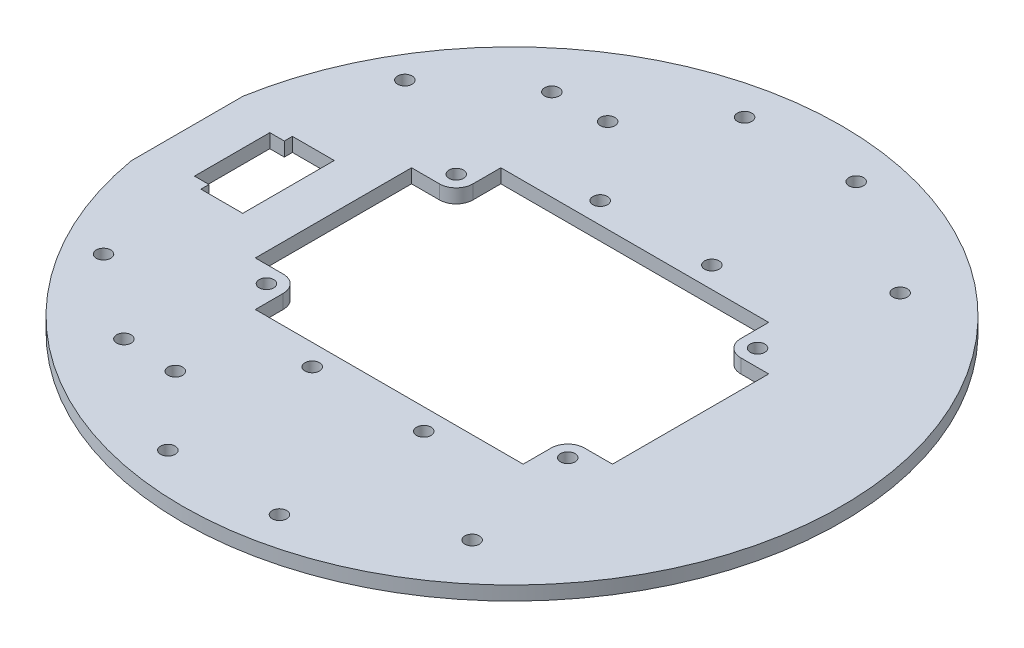
SolidWorks part; units mm, degrees
material "Acrylic (Medium-high impact)"
ref_plane "Front Plane" through (0, 0, 0) normal (0, 0, 1) x (1, 0, 0)
ref_plane "Top Plane" through (0, 0, 0) normal (0, 1, 0) x (1, 0, 0)
ref_plane "Right Plane" through (0, 0, 0) normal (1, 0, 0) x (0, 0, -1)
sketch "Sketch1" plane through (0, 0, 0) normal (0, 1, 0) x (1, 0, 0)
  line L0 (-73.9169, 12.7) -> (-73.9169, -12.7)
  line L1 (-73.9169, 12.7) -> (-73.9169, -12.7) construction
  line L2 (-34.29, 21.59) -> (34.29, 21.59) construction
  line L3 (34.29, 21.59) -> (34.29, -21.59) construction
  line L4 (34.29, -21.59) -> (-34.29, -21.59) construction
  line L5 (-34.29, -21.59) -> (-34.29, 21.59) construction
  line L6 (0, 21.59) -> (0, 75) construction
  line L7 (34.29, 0) -> (75, 0) construction
  line L8 (0, -25.4) -> (0, -21.59) construction
  line L9 (-34.29, 0) -> (-38.1, 0) construction
  line L10 (-30.48, 27.94) -> (30.48, 27.94)
  line L11 (-30.48, 27.94) -> (-30.48, 21.59)
  line L12 (0, 21.59) -> (0, 27.94) construction
  line L13 (30.48, 27.94) -> (30.48, 21.59)
  line L14 (34.29, 17.78) -> (40.64, 17.78)
  line L16 (34.29, -17.78) -> (40.64, -17.78)
  line L17 (40.64, 17.78) -> (40.64, -17.78)
  line L19 (30.48, -21.59) -> (30.48, -27.94)
  line L20 (30.48, -27.94) -> (-30.48, -27.94)
  line L21 (-30.48, -21.59) -> (-30.48, -27.94)
  line L22 (-40.64, -17.78) -> (-34.29, -17.78)
  line L23 (-40.64, -17.78) -> (-40.64, 17.78)
  line L24 (-40.64, 17.78) -> (-34.29, 17.78)
  line L28 (-24.25, -35.9484) -> (24.25, -35.9484) construction
  line L29 (24.25, -35.9484) -> (24.25, -62.4484) construction
  line L30 (-12.7, -35.9484) -> (-12.7, -32.7734) construction
  line L31 (24.25, -62.4484) -> (-24.25, -62.4484) construction
  line L32 (-24.25, -62.4484) -> (-24.25, -35.9484) construction
  line L33 (-24.25, -62.4484) -> (-27.1489, -69.9138) construction
  line L34 (24.25, -62.4484) -> (27.1489, -69.9138) construction
  line L35 (-24.25, -35.9484) -> (-24.25, -27.94) construction
  line L36 (0, -35.9484) -> (0, -62.4484) construction
  line L37 (-50.865, 0) -> (-40.64, 0) construction
  line L38 (-27.425, -49.1984) -> (-24.25, -49.1984) construction
  line L39 (-12.7, -65.6234) -> (-12.7, -62.4484) construction
  line L40 (-63.692, 8.5725) -> (-60.39, 8.5725)
  line L41 (-63.692, 8.5725) -> (-63.692, -8.5725)
  line L42 (-63.692, -8.5725) -> (-60.39, -8.5725)
  line L43 (-50.865, 8.5725) -> (-50.865, -8.5725)
  line L44 (-60.39, 8.5725) -> (-60.39, 10.414)
  line L45 (-60.39, 10.414) -> (-50.865, 10.414)
  line L46 (-50.865, 10.414) -> (-50.865, 8.5725)
  line L47 (-60.39, -8.5725) -> (-60.39, -10.414)
  line L48 (-60.39, -10.414) -> (-50.865, -10.414)
  line L49 (-50.865, -10.414) -> (-50.865, -8.5725)
  line L50 (-63.692, 0) -> (-73.9169, 0) construction
  line L51 (55.1757, 50.8) -> (55.1757, -50.8) construction
  arc A0 (-73.9169, -12.7) -> (-73.9169, 12.7) centre (0, 0) ccw
  arc A1 (55.356, -50.6035) -> (55.356, 50.6035) centre (0, 0) ccw construction
  circle A2 centre (-34.29, 21.59) radius 1.651
  circle A3 centre (34.29, 21.59) radius 1.651
  circle A4 centre (-34.29, -21.59) radius 1.651
  circle A5 centre (34.29, -21.59) radius 1.651
  circle A6 centre (-39.6269, 48.6985) radius 1.651 construction
  circle A7 centre (39.6269, -48.6985) radius 1.651
  circle A8 centre (-39.6269, -48.6985) radius 1.651
  circle A9 centre (-58.6769, -34.29) radius 1.651
  circle A10 centre (-58.6769, 34.29) radius 1.651
  circle A11 centre (-39.6269, 48.6985) radius 1.651
  circle A12 centre (39.6269, 48.6985) radius 1.651
  circle A13 centre (39.6269, -48.6985) radius 1.651 construction
  circle A14 centre (12.7, -65.6234) radius 1.651
  circle A15 centre (12.7, -32.7734) radius 1.651
  circle A16 centre (12.7, 32.7734) radius 1.651
  circle A17 centre (12.7, 65.6234) radius 1.651
  arc A18 (-34.29, 17.78) -> (-30.48, 21.59) centre (-34.29, 21.59) ccw
  arc A19 (-34.29, -17.78) -> (-30.48, -21.59) centre (-34.29, -21.59) cw
  arc A20 (30.48, 21.59) -> (34.29, 17.78) centre (34.29, 21.59) ccw
  arc A21 (30.48, -21.59) -> (34.29, -17.78) centre (34.29, -21.59) cw
  circle A22 centre (-27.425, -49.1984) radius 1.651
  circle A23 centre (-12.7, -32.7734) radius 1.651
  circle A24 centre (-12.7, -65.6234) radius 1.651
  circle A25 centre (-12.7, 65.6234) radius 1.651
  circle A26 centre (-27.425, 49.1984) radius 1.651
  circle A27 centre (-12.7, 32.7734) radius 1.651
  dimension "D11" = 3.302
  dimension "D1" = 68.58
  dimension "D2" = 43.18
  dimension "D3" = 3.81
  dimension "D4" = 6.35
  dimension "D5" = 60.96
  dimension "D6" = 35.56
  dimension "D7" = 48.5
  dimension "D8" = 26.5
  dimension "D9" = 12.7
  dimension "D10" = 3.175
  dimension "D12" = 17.145
  dimension "D14" = 101.6
  dimension "D15" = 3.302
  dimension "D16" = 20.828
  dimension "D17" = 9.525
extrude "Boss-Extrude1" add sketch "Sketch1" along normal blind 3.175
